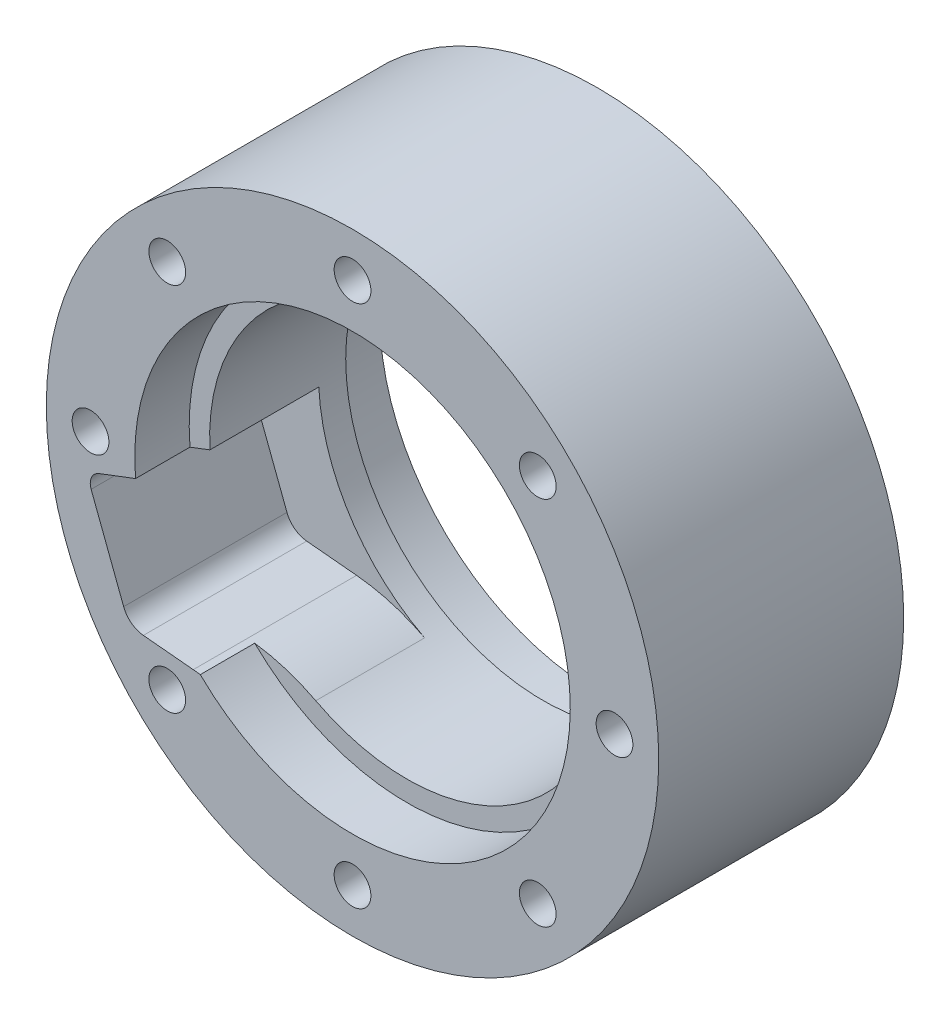
SolidWorks part; units mm, degrees
ref_plane "Front Plane" through (0, 0, 0) normal (0, 0, 1) x (1, 0, 0)
ref_plane "Top Plane" through (0, 0, 0) normal (0, 1, 0) x (1, 0, 0)
ref_plane "Right Plane" through (0, 0, 0) normal (1, 0, 0) x (0, 0, -1)
ref_axis "Z" through (0, 0, 9.9) along (0, 0, -1)
sketch "Sketch7" plane through (0, 0, 0) normal (0, 1, 0) x (1, 0, 0)
  line L0 (16, 9) -> (16, 5)
  line L2 (16, 5) -> (14.5, 5)
  line L5 (16, 9) -> (22.5, 9)
  line L6 (22.5, 9) -> (22.5, -9)
  line L7 (24.7452, 0) -> (-6.4078, 0) construction
  line L8 (16, -5) -> (14.5, -5)
  line L9 (16, -9) -> (16, -5)
  line L10 (14.5, 5) -> (14.5, -5)
  line L11 (22.5, -9) -> (16, -9)
  line L12 (0, -9.9) -> (0, 9.9) construction
  dimension "D2" = 4
  dimension "D4" = 5
  dimension "D1" = 14.5
  dimension "D3" = 16
  dimension "D5" = 22.5
revolve "Revolve1" add sketch "Sketch7" angle 360 about axis through (0, 0, 9.9) along (0, 0, -1)
sketch "Sketch3" plane through (0, 0, 0) normal (0, 0, 1) x (1, 0, 0)
  line L0 (0, 0) -> (0, 19.25) construction
  circle A0 centre (0, 19.25) radius 1.35
  dimension "D1" = 2.7
  dimension "D2" = 19.25
extrude "Cut-Extrude2" cut sketch "Sketch3" against normal through all both and the other way through all
sketch "Sketch4" plane through (0, 0, -9) normal (0, 0, -1) x (-1, 0, 0)
  circle A0 centre (0, 19.25) radius 2.25
  circle A1 centre (0, 19.25) radius 1.35 construction
  dimension "D1" = 4.5
extrude "Cut-Extrude4" cut sketch "Sketch4" against normal blind 2.5 and the other way through all
chamfer "Chamfer1" distance 0.1 angle 45 1 edges at (-1.35, 19.25, -6.5)
pattern_circular "CirPattern3" count 4 over 360 about axis through (0, 0, 9.9) along (0, 0, -1) of "Cut-Extrude4"
pattern_circular "CirPattern2" count 8 over 360 about axis through (0, 0, 9.9) along (0, 0, -1) of "Cut-Extrude2"
sketch "Sketch11" plane through (0, 0, 0) normal (0, 0, 1) x (1, 0, 0)
  line L0 (-1.5717, 4.1277) -> (0, 0)
  line L1 (0, 0) -> (-17.99, -6.8501) construction
  line L2 (-15.3679, -11.0348) -> (-11.7013, -11.3815)
  line L4 (0, 0) -> (-6.7001, -12.8592)
  line L5 (-16.8164, -9.9323) -> (-19.2058, -3.657)
  line L6 (-18.6271, -2.3666) -> (-1.5717, 4.1277)
  arc A0 (-11.7013, -11.3815) -> (-6.7001, -12.8592) centre (-12.9808, -24.9136) cw
  arc A1 (-18.6271, -2.3666) -> (-19.2058, -3.657) centre (-18.2713, -3.3011) ccw
  arc A2 (-15.3679, -11.0348) -> (-16.8164, -9.9323) centre (-15.2057, -9.319) cw
  circle A3 centre (0, 0) radius 14.5 construction
  point P10 (-16.3003, -6.9959)
  point P11 (-15.1118, -10.4211)
  point P12 (-18.1895, -3.5812)
  point P13 (0, 0)
  point P14 (-8.4978, -11.7489)
  point P17 (-15.5562, -10.2713)
  point P18 (-19.2058, -3.657)
  point P19 (-14.8547, -11.0881)
  point P20 (-6.7001, -12.8592)
  point P22 (-11.7013, -11.3815)
  dimension "D2" = 1
  dimension "D1" = 19.25
extrude "Cut-Extrude6" cut sketch "Sketch11" along normal blind 10 and the other way blind 3
equation "\"BearingBaseDistance\"= 10"
equation "\"BearingOD\"= 32"
equation "\"BearingHeight\"= 4"
equation "\"SeatsOD\"= \"BearingOD\" + 10"
equation "\"WireHarnessHeight\"= 4"
equation "\"OuterWallWidth\"= 6"
equation "\"OverallOD\" = 45"
equation "\"BearingID\" = 25"
equation "\"OverallHeight\"= \"WireHarnessHeight\" + \"BearingHeight\"*2 + \"BearingBaseDistance\""
equation "\"RetainingRingThickness\" = 1.30"
equation "\"RetaininRingGrooveDiameter\" = 23.9"
equation "\"ShaftLengthAfterFlange\" = 2*\"BearingHeight\" + \"BearingBaseDistance\" + \"RetainingRingThickness\"*2\t'give a retaining ring thickness of extra clearance"
equation "\"RetainingRingGrooveBase\" = \"ShaftLengthAfterFlange\" - \"RetainingRingThickness\"*2"
equation "\"CoverThickness\" = 1"
equation "\"CoverClearance\" = 1"
equation "\"FlangHeight\" = 3"
equation "\"OuterHousingHeight\" = \"WireHarnessHeight\" + \"BearingHeight\"*2 + \"BearingBaseDistance\""
equation "\"PCBWidth\" = 5"
equation "\"PCBHeight\" = \"OuterHousingHeight\" "
equation "\"PCBThickness\" = 1"
equation "\"NormalDistSidewallPCBToZ\" = (\"OverallOD\"/2) - 1.6\t'radial distance from the z axis to pcb origin on the top/connector side"
equation "\"PCBSidewallCutoutClearance\" = 0.1"
equation "\"D3@Sketch7\"=\"BearingOD\"/2"
equation "\"D4@Sketch7\"=\"BearingBaseDistance\"/2"
equation "\"D5@Sketch7\"=\"OverallOD\"/2"
equation "\"D2@Sketch3\"=(\"OverallOD\"+\"BearingOD\")/4"
equation "\"OutputHubBoltCircleRadius\" = 8"
equation "\"OutputHubOD\" = 27"
equation "\"BearingInnerRaceOD\" = 26.9"
equation "\"StatorWireRadius\" = \"NormalDistSidewallPCBToZ\" - 5.7"
equation "\"MountingHoleRadius\" = (\"OverallOD\"+\"BearingOD\")/4"
equation "\"D1@Sketch11\"=\"MountingHoleRadius\""
